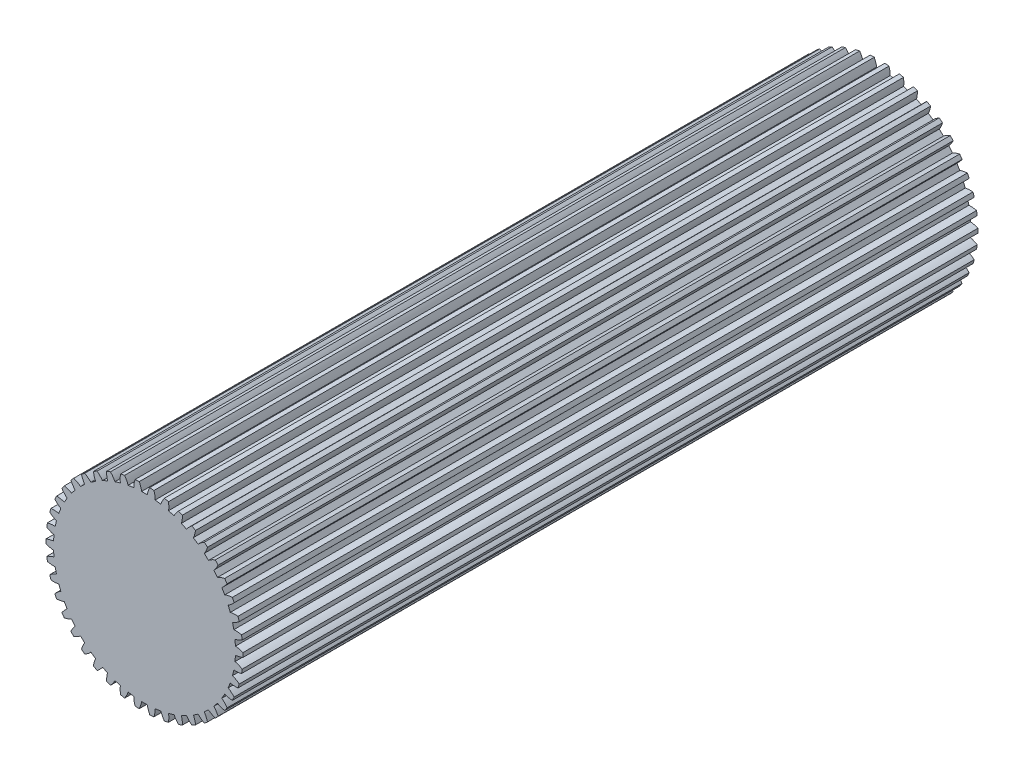
SolidWorks part; units mm, degrees
material "Brass"
ref_plane "Front Plane" through (0, 0, 0) normal (0, 0, 1) x (1, 0, 0)
ref_plane "Top Plane" through (0, 0, 0) normal (0, 1, 0) x (1, 0, 0)
ref_plane "Right Plane" through (0, 0, 0) normal (1, 0, 0) x (0, 0, -1)
sketch "Sketch1" plane through (0, 0, 0) normal (0, 0, 1) x (1, 0, 0)
  circle A0 centre (0, 0) radius 18.6267
  dimension "D1" = 37.2533
extrude "Boss-Extrude1" add sketch "Sketch1" along normal blind 139
sketch "Sketch2" plane through (0, 0, 0) normal (0, 0, 1) x (1, 0, 0)
  spline S0 degree 4 poles (17.1978, 0.739) (17.2039, 0.7392) (17.2154, 0.7393) (17.2343, 0.7391) (17.2715, 0.7379) (17.3137, 0.7353) (17.3614, 0.7312) (17.4127, 0.7257) (17.4566, 0.7203) (17.5005, 0.7141) (17.5443, 0.7075) (17.5973, 0.6986) (17.661, 0.6871) (17.7355, 0.6721) (17.8202, 0.6533) (17.9066, 0.6324) (17.9918, 0.6103) (18.078, 0.5862) (18.1615, 0.5616) (18.2484, 0.5343) (18.3286, 0.5082) (18.4188, 0.4769) (18.4915, 0.451) (18.5877, 0.4148) (18.6446, 0.3928) (18.7113, 0.3663) (18.7409, 0.3541) (18.7591, 0.3466) knots 0 0 0 0 0 0.015084 0.028532 0.04661 0.092111 0.119476 0.146842 0.174209 0.201575 0.228941 0.256307 0.307035 0.361767 0.4165 0.471232 0.525964 0.580697 0.635429 0.690161 0.744894 0.799626 0.854358 0.909091 0.954545 1 1 1 1 1 construction
  spline S1 degree 4 poles (17.1978, 0.739) (17.2039, 0.7392) (17.2154, 0.7393) (17.2343, 0.7391) (17.2715, 0.7379) (17.3137, 0.7353) (17.3614, 0.7312) (17.4127, 0.7257) (17.4566, 0.7203) (17.5005, 0.7141) (17.5443, 0.7075) (17.5973, 0.6986) (17.661, 0.6871) (17.7355, 0.6721) (17.8202, 0.6533) (17.9066, 0.6324) (17.9918, 0.6103) (18.078, 0.5862) (18.1615, 0.5616) (18.2484, 0.5343) (18.3286, 0.5082) (18.4188, 0.4769) (18.4915, 0.451) (18.5669, 0.4227) (18.6036, 0.4086) (18.6223, 0.4013) knots 0 0 0 0 0 0.015084 0.028532 0.04661 0.092111 0.119476 0.146842 0.174209 0.201575 0.228941 0.256307 0.307035 0.361767 0.4165 0.471232 0.525964 0.580697 0.635429 0.690161 0.744894 0.799626 0.854358 0.909091 0.909091 0.909091 0.909091 0.909091
  spline S2 degree 4 poles (17.1159, 1.8324) (17.1219, 1.8331) (17.1333, 1.8348) (17.152, 1.8378) (17.1886, 1.8446) (17.2299, 1.8534) (17.2765, 1.8645) (17.3264, 1.8776) (17.369, 1.8896) (17.4115, 1.9022) (17.4538, 1.9153) (17.5049, 1.9319) (17.5661, 1.9529) (17.6376, 1.9788) (17.7185, 2.0099) (17.8009, 2.0435) (17.8818, 2.0781) (17.9634, 2.1148) (18.0423, 2.1515) (18.1242, 2.1915) (18.1997, 2.2293) (18.2841, 2.2736) (18.3522, 2.31) (18.442, 2.3602) (18.4949, 2.3904) (18.5569, 2.4266) (18.5843, 2.4431) (18.6013, 2.4532) knots 0 0 0 0 0 0.015084 0.028532 0.04661 0.092111 0.119476 0.146842 0.174209 0.201575 0.228941 0.256307 0.307035 0.361767 0.4165 0.471232 0.525964 0.580697 0.635429 0.690161 0.744894 0.799626 0.854358 0.909091 0.954545 1 1 1 1 1 construction
  spline S3 degree 4 poles (17.1159, 1.8324) (17.1219, 1.8331) (17.1333, 1.8348) (17.152, 1.8378) (17.1886, 1.8446) (17.2299, 1.8534) (17.2765, 1.8645) (17.3264, 1.8776) (17.369, 1.8896) (17.4115, 1.9022) (17.4538, 1.9153) (17.5049, 1.9319) (17.5661, 1.9529) (17.6376, 1.9788) (17.7185, 2.0099) (17.8009, 2.0435) (17.8818, 2.0781) (17.9634, 2.1148) (18.0423, 2.1515) (18.1242, 2.1915) (18.1997, 2.2293) (18.2841, 2.2736) (18.3522, 2.31) (18.4225, 2.3493) (18.4567, 2.3687) (18.4742, 2.3787) knots 0 0 0 0 0 0.015084 0.028532 0.04661 0.092111 0.119476 0.146842 0.174209 0.201575 0.228941 0.256307 0.307035 0.361767 0.4165 0.471232 0.525964 0.580697 0.635429 0.690161 0.744894 0.799626 0.854358 0.909091 0.909091 0.909091 0.909091 0.909091
  spline S4 degree 1 poles (17.1159, 1.8324) (17.1978, 0.739) knots 0 0 1 1 construction
  spline S5 degree 1 poles (17.1159, 1.8324) (17.1978, 0.739) knots 0 0 1 1
  spline S6 degree 1 poles (18.6223, 0.4013) (59.9861, 1.2927) knots 0 0 1 1 construction
  spline S7 degree 1 poles (18.6223, 0.4013) (59.9861, 1.2927) knots 0 0 1 1
  spline S8 degree 4 poles (59.9965, 0.6495) (59.996, 0.6954) (59.9948, 0.7841) (59.9935, 0.9041) (59.9876, 1.2291) (59.9845, 1.3714) (59.9739, 1.7905) (59.9657, 2.0284) (59.9537, 2.3723) (59.9415, 2.6523) (59.9269, 2.9708) (59.9113, 3.2659) (59.8938, 3.5749) (59.875, 3.8756) (59.8545, 4.1808) (59.8325, 4.4838) (59.8091, 4.7868) (59.7838, 5.0915) (59.7577, 5.3917) (59.7289, 5.6999) (59.7003, 5.9941) (59.6673, 6.3111) (59.6376, 6.5899) (59.5983, 6.9317) (59.5709, 7.1681) (59.5189, 7.5842) (59.5007, 7.7253) (59.4582, 8.0476) (59.4416, 8.1664) (59.4295, 8.2543) (59.4232, 8.2997) knots 0 0 0 0 0 0.020959 0.041918 0.083333 0.123016 0.162698 0.202381 0.242063 0.281746 0.321429 0.361111 0.400794 0.440476 0.480159 0.519841 0.559524 0.599206 0.638889 0.678571 0.718254 0.757937 0.797619 0.837302 0.876984 0.916667 0.958082 0.979041 1 1 1 1 1 construction
  spline S9 degree 4 poles (59.9861, 1.2927) (59.9847, 1.3561) (59.9818, 1.4796) (59.9739, 1.7905) (59.9657, 2.0284) (59.9537, 2.3723) (59.9415, 2.6523) (59.9269, 2.9708) (59.9113, 3.2659) (59.8938, 3.5749) (59.875, 3.8756) (59.8545, 4.1808) (59.8325, 4.4838) (59.8091, 4.7868) (59.7838, 5.0915) (59.7577, 5.3917) (59.7289, 5.6999) (59.7003, 5.9941) (59.6673, 6.3111) (59.6376, 6.5899) (59.5983, 6.9317) (59.5709, 7.1681) (59.5324, 7.4768) (59.5168, 7.5993) (59.5087, 7.6622) knots 0.083333 0.083333 0.083333 0.083333 0.083333 0.123016 0.162698 0.202381 0.242063 0.281746 0.321429 0.361111 0.400794 0.440476 0.480159 0.519841 0.559524 0.599206 0.638889 0.678571 0.718254 0.757937 0.797619 0.837302 0.876984 0.916667 0.916667 0.916667 0.916667 0.916667
  spline S10 degree 1 poles (59.5087, 7.6622) (18.4742, 2.3787) knots 0 0 1 1 construction
  spline S11 degree 1 poles (59.5087, 7.6622) (18.4742, 2.3787) knots 0 0 1 1
extrude "Cut-Extrude2" cut sketch "Sketch2" against normal blind 140 and the other way blind 140
ref_axis "Axis1" through (0, 0, -6.95) along (0, 0, 1)
pattern_circular "CirPattern1" count 42 over 360 about axis through (0, 0, -6.95) along (0, 0, 1) of "Cut-Extrude2"
